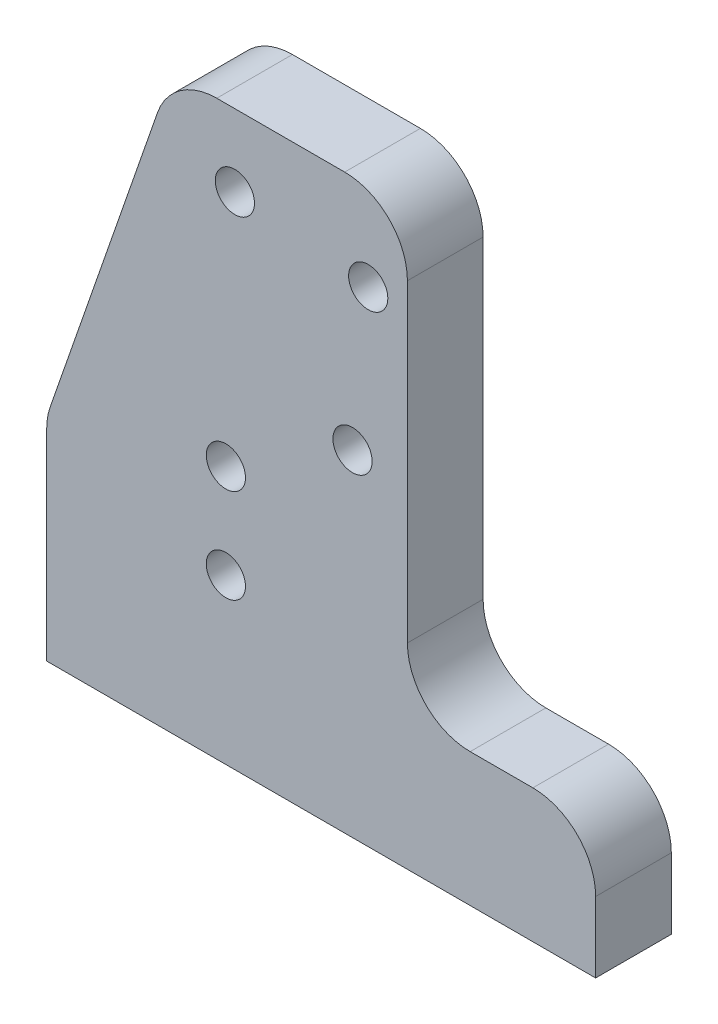
SolidWorks part; units mm, degrees
other "Markup1"
sketch "Sketch26" plane through (35, 0, 4.826) normal (0.2759, -0.8282, 0.4878) x (0.8301, -0.0505, -0.5553)
material "6061 Alloy"
ref_plane "Front" through (0, 0, 0) normal (0, 0, 1) x (1, 0, 0)
ref_plane "Top" through (0, 0, 0) normal (0, 1, 0) x (1, 0, 0)
ref_plane "Right" through (0, 0, 0) normal (1, 0, 0) x (0, 0, -1)
sketch "Sketch1" plane through (0, 0, 0) normal (0, 0, 1) x (1, 0, 0)
  line L0 (0, 0) -> (0, 13.5)
  line L9 (35, 0) -> (0, 0)
  line L15 (8, 36.5) -> (23, 36.5)
  line L16 (23, 36.5) -> (23, 8.5)
  line L17 (23, 8.5) -> (35, 8.5)
  line L18 (35, 8.5) -> (35, 0)
  line L22 (8, 36.5) -> (0, 13.5)
  dimension "D3" = 13.5
  dimension "D1" = 35
  dimension "D2" = 12
  dimension "D4" = 15
  dimension "D5" = 36.5
  dimension "D6" = 8.5
extrude "Boss-Extrude1" add sketch "Sketch1" along normal blind 4.826 contours L9 region at (14.5579, 15.4228, 0)
hole_wizard "M3x0.5 Tapped Hole2" positions "Sketch13" profile "Sketch14" tap size "M3x0.5" standard "ANSI Metric" end condition through all
sketch "Sketch13" plane through (0, 0, 4.826) normal (0, 0, 1) x (1, 0, 0)
  line L3 (8, 36.5) -> (23, 36.5) construction
  point P5 (12, 31.9)
  dimension "D1" = 4.6
  dimension "D2" = 12
sketch "Sketch14" plane through (12, 31.9, 4.826) normal (1, 0, 0) x (0, -1, 0)
  line L0 (0, 0) -> (0, 4.826)
  line L1 (0, 4.826) -> (1.25, 4.826)
  line L2 (1.25, 4.826) -> (1.25, 0)
  line L5 (1.25, 0) -> (0, 0)
  line L11 (0, -6.35) -> (0, 107.95) construction
  dimension "Thru Tap Drill Dia." = 2.5
  dimension "Thru Tap Drill Depth" = 4.826
cosmetic thread "Hole Thread1" parameters "D2"=3
sketch "Sketch16" plane through (0, 0, 0) normal (0, -1, 0) x (1, 0, 0)
  line L0 (0, 4.826) -> (0, 0) construction
  line L3 (0, 2.413) -> (42.6944, 2.413) construction
  point P0 (28.73, 2.413)
  point P1 (16.73, 2.413)
  dimension "D1" = 16.73
  dimension "D2" = 12
hole_wizard "M3x0.5 Tapped Hole3" positions "Sketch17" profile "Sketch18" tap size "M3x0.5" standard "ANSI Metric"
sketch "Sketch17" plane through (0, 0, 0) normal (0, -1, 0) x (-1, 0, 0)
  point P0 (-16.73, -2.413)
  point P3 (-28.73, -2.413)
sketch "Sketch18" plane through (16.73, 0, 2.413) normal (1, 0, 0) x (0, 0, -1)
  line L0 (0, 0) -> (0, 5.7511)
  line L1 (0, 5.7511) -> (1.25, 5)
  line L2 (1.25, 5) -> (1.25, 0)
  line L5 (1.25, 0) -> (0, 0)
  line L10 (0, 5.7511) -> (-1.25, 5) construction
  line L11 (0, -6.35) -> (0, 107.95) construction
  dimension "Tap Drill Dia." = 2.5
  dimension "Tap Drill Depth" = 5
  dimension "Drill Angle" = 118
cosmetic thread "Hole Thread6" parameters "D1"=6, "D2"=3
cosmetic thread "Hole Thread7" parameters "D1"=6, "D2"=3
fillet "Fillet2" radius 4 5 edges at (35, 8.5, 2.413) (23, 8.5, 2.413) (23, 36.5, 2.413) (0, 13.5, 2.413) (8, 36.5, 2.413)
sketch "Sketch19" plane through (0, 0, 4.826) normal (0, 0, 1) x (1, 0, 0)
  circle A0 centre (19.5, 21.4) radius 1.4
  circle A1 centre (12, 31.9) radius 1.25 construction
  dimension "D3" = 2.8
  dimension "D1" = 10.5
  dimension "D2" = 7.5
sketch "Sketch23" plane through (0, 0, 4.826) normal (0, 0, 1) x (1, 0, 0)
  circle A0 centre (20.5, 30.9) radius 1.25
  circle A1 centre (12, 31.9) radius 1.25 construction
  dimension "D3" = 2.5
  dimension "D1" = 8.5
  dimension "D2" = 1
sketch "Sketch28" plane through (0, 0, 4.826) normal (0, 0, 1) x (1, 0, 0)
  circle A0 centre (11.425, 16.46) radius 1.4
  circle A1 centre (11.425, 10.46) radius 1.4
  circle A2 centre (12, 31.9) radius 1.25 construction
  dimension "D3" = 2.8
  dimension "D1" = 15.44
  dimension "D2" = 6
  dimension "D5" = 0.575
hole_wizard "M3x0.5 Tapped Hole4" positions "Sketch29" profile "Sketch30" tap size "M3x0.5" standard "ANSI Metric" end condition through all
sketch "Sketch29" plane through (0, 0, 4.826) normal (0, 0, 1) x (1, 0, 0)
  point P0 (19.5, 21.4)
  point P3 (20.5, 30.9)
sketch "Sketch30" plane through (19.5, 21.4, 4.826) normal (1, 0, 0) x (0, -1, 0)
  line L0 (0, 0) -> (0, 4.826)
  line L1 (0, 4.826) -> (1.25, 4.826)
  line L2 (1.25, 4.826) -> (1.25, 0)
  line L5 (1.25, 0) -> (0, 0)
  line L11 (0, -6.35) -> (0, 107.95) construction
  dimension "Thru Tap Drill Dia." = 2.5
  dimension "Thru Tap Drill Depth" = 4.826
cosmetic thread "Hole Thread2" parameters "D2"=3
cosmetic thread "Hole Thread3" parameters "D2"=3
hole_wizard "M3x0.5 Tapped Hole5" positions "Sketch33" profile "Sketch34" tap size "M3x0.5" standard "ANSI Metric" end condition through all
sketch "Sketch33" plane through (0, 0, 4.826) normal (0, 0, 1) x (1, 0, 0)
  point P0 (11.425, 16.46)
  point P3 (11.425, 10.46)
sketch "Sketch34" plane through (11.425, 16.46, 4.826) normal (1, 0, 0) x (0, -1, 0)
  line L0 (0, 0) -> (0, 4.826)
  line L1 (0, 4.826) -> (1.25, 4.826)
  line L2 (1.25, 4.826) -> (1.25, 0)
  line L5 (1.25, 0) -> (0, 0)
  line L11 (0, -6.35) -> (0, 107.95) construction
  dimension "Thru Tap Drill Dia." = 2.5
  dimension "Thru Tap Drill Depth" = 4.826
cosmetic thread "Hole Thread4" parameters "D2"=3
cosmetic thread "Hole Thread5" parameters "D2"=3
